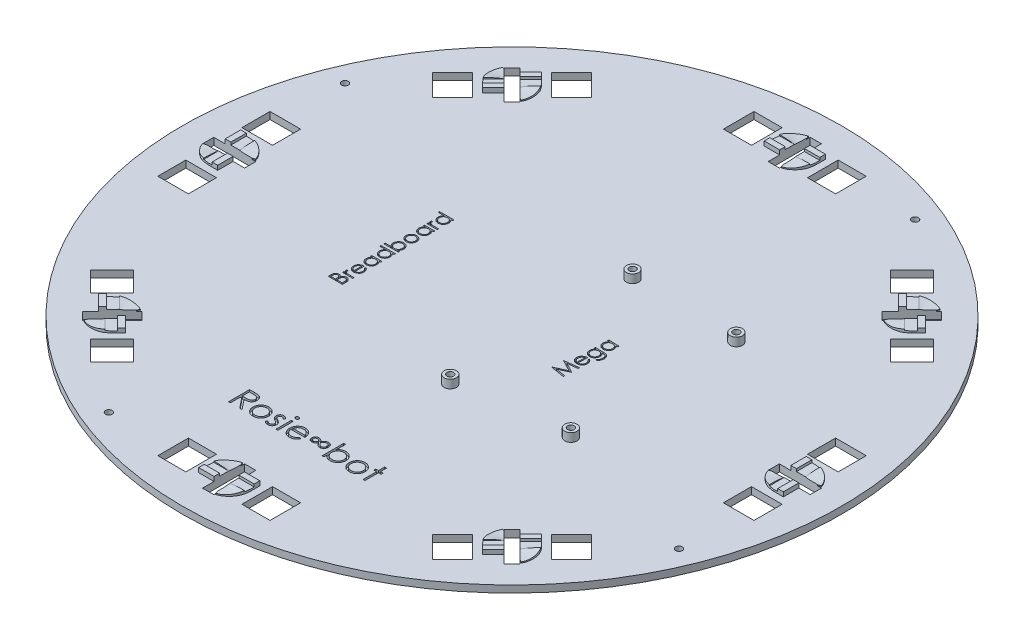
SolidWorks part; units mm, degrees
ref_plane "Front" through (0, 0, 0) normal (0, 0, 1) x (1, 0, 0)
ref_plane "Top" through (0, 0, 0) normal (0, 1, 0) x (1, 0, 0)
ref_plane "Right" through (0, 0, 0) normal (1, 0, 0) x (0, 0, -1)
sketch "Sketch1" plane through (0, 0, 0) normal (0, 1, 0) x (1, 0, 0)
  circle A0 centre (0, 0) radius 149.225
  dimension "D1" = 298.45
extrude "Boss-Extrude1" add sketch "Sketch1" along normal blind 3.175 contours A0
sketch "Sketch2" plane through (0, 3.175, 0) normal (0, 1, 0) x (1, 0, 0)
  line L1 (-2.54, -137.5833) -> (2.54, -137.5833)
  line L2 (-2.54, -137.5833) -> (-2.54, -118.5333)
  line L3 (-2.54, -118.5333) -> (2.54, -118.5333)
  line L4 (2.54, -137.5833) -> (2.54, -118.5333)
  circle A0 centre (0, 0) radius 149.225 construction
  point P4 (0, -118.5333)
  dimension "D1" = 5.08
  dimension "D2" = 19.05
  dimension "D3" = 137.5833
extrude "Cut-Extrude1" cut sketch "Sketch2" against normal up to next and the other way through all contours L1 L4 L3 L2
sketch "Sketch4" plane through (0, 3.175, 0) normal (0, 1, 0) x (1, 0, 0)
  line L0 (0, -128.0583) -> (-2.9434, -118.9995) construction
  line L1 (-2.9434, -118.9995) -> (0, -128.0583) construction
  line L2 (0, -128.0583) -> (-5.5987, -120.3525) construction
  line L3 (0, -128.0583) -> (-7.7059, -122.4597) construction
  line L4 (0, -128.0583) -> (-9.0588, -125.115) construction
  line L5 (0, -128.0583) -> (-9.525, -128.0583) construction
  line L9 (2.54, -118.5333) -> (-2.54, -118.5333) construction
  line L10 (2.54, -118.5333) -> (2.54, -137.5833) construction
  line L11 (-2.54, -118.5333) -> (-2.54, -137.5833) construction
  line L12 (2.54, -137.5833) -> (-2.54, -137.5833) construction
  circle A0 centre (0, -128.0583) radius 9.525 construction
  point P16 (0, -118.5333)
  point P19 (2.54, -128.0583)
  dimension "D1" = 18
  dimension "D2" = 18
  dimension "D3" = 18
  dimension "D4" = 18
  dimension "D5" = 18
ref_plane "Plane1" through (-37.6354, 0, 12.2285) normal (0.9511, 0, -0.309) x (-0.309, 0, -0.9511)
ref_plane "Plane2" through (-60.8954, 0, 44.2431) normal (0.809, 0, -0.5878) x (-0.5878, 0, -0.809)
ref_plane "Plane3" through (-60.8954, 0, 83.8153) normal (0.5878, 0, -0.809) x (-0.809, 0, -0.5878)
ref_plane "Plane4" through (-37.6354, 0, 115.8299) normal (0.309, 0, -0.9511) x (-0.9511, 0, -0.309)
ref_plane "Plane5" through (0, 0, 128.0583) normal (0, 0, -1) x (-1, 0, 0)
sketch "Sketch5" plane through (-37.6354, 0, 12.2285) normal (0.9511, 0, -0.309) x (-0.309, 0, -0.9511)
  line L0 (-111.947, 3.175) -> (-130.0646, 3.175) construction
  line L1 (-113.5711, 3.175) -> (-112.2657, 3.175)
  line L2 (-113.5711, 3.175) -> (-113.5711, 3.683)
  line L3 (-113.5711, 3.683) -> (-112.2657, 3.683)
  line L4 (-112.2657, 3.175) -> (-112.2657, 3.683)
  dimension "D2" = 0.508
sketch "Sketch6" plane through (-60.8954, 0, 44.2431) normal (0.809, 0, -0.5878) x (-0.5878, 0, -0.809)
  line L0 (-94.4025, 3.175) -> (-109.8143, 3.175) construction
  line L1 (-99.2801, 3.175) -> (-94.0764, 3.175)
  line L2 (-99.2801, 3.175) -> (-99.2801, 3.775)
  line L3 (-99.2801, 3.775) -> (-94.0764, 3.775)
  line L4 (-94.0764, 3.175) -> (-94.0764, 3.775)
  dimension "D2" = 0.6
sketch "Sketch7" plane through (-60.8954, 0, 83.8153) normal (0.5878, 0, -0.809) x (-0.809, 0, -0.5878)
  line L0 (-67.6172, 3.175) -> (-78.8146, 3.175) construction
  line L1 (-72.1312, 3.175) -> (-65.7458, 3.175)
  line L2 (-72.1312, 3.175) -> (-72.1312, 4.075)
  line L3 (-72.1312, 4.075) -> (-65.7458, 4.075)
  line L4 (-65.7458, 3.175) -> (-65.7458, 4.075)
  dimension "D2" = 0.9
sketch "Sketch10" plane through (-37.6354, 0, 115.8299) normal (0.309, 0, -0.9511) x (-0.9511, 0, -0.309)
  line L0 (-39.5722, 3.175) -> (-30.5134, 3.175) construction
  line L1 (-36.9015, 3.175) -> (-30.0472, 3.175)
  line L2 (-36.9015, 3.175) -> (-36.9015, 4.475)
  line L3 (-36.9015, 4.475) -> (-30.0472, 4.475)
  line L4 (-30.0472, 3.175) -> (-30.0472, 4.475)
  dimension "D3" = 1.3
sketch "Sketch11" plane through (0, 0, 128.0583) normal (0, 0, -1) x (-1, 0, 0)
  line L0 (0, 3.175) -> (9.525, 3.175) construction
  line L1 (2.54, 3.175) -> (9.525, 3.175)
  line L2 (2.54, 3.175) -> (2.54, 4.575)
  line L3 (2.54, 4.575) -> (9.525, 4.575)
  line L4 (9.525, 3.175) -> (9.525, 4.575)
  dimension "D3" = 1.4
loft "Loft1" add profiles "Sketch5", "Sketch6", "Sketch7", "Sketch10", "Sketch11" connector at (-2.54, 3.683, 120.241) connector at (-2.54, 3.775, 124.5623) connector at (-2.54, 4.075, 126.2129) connector at (-2.54, 4.475, 127.233) connector at (-2.54, 4.575, 128.0583)
sketch "Sketch13" plane through (-104.9799, 0, 128.0583) normal (0, 0, -1) x (-1, 0, 0)
  line L6 (-95.4549, 3.175) -> (-102.4399, 3.175)
  line L7 (-95.4549, 3.175) -> (-95.4549, 4.575)
  line L8 (-95.4549, 4.575) -> (-102.4399, 4.575)
  line L9 (-102.4399, 3.175) -> (-102.4399, 4.575)
extrude "Boss-Extrude4" add sketch "Sketch13" against normal blind 1.7907
sketch "Sketch25" plane through (0, 0, 129.849) normal (0, 0, 1) x (1, 0, 0)
  line L0 (-9.525, 4.575) -> (-2.54, 4.575) construction
  line L1 (-9.525, 3.175) -> (-2.54, 3.175)
  line L2 (-9.525, 3.175) -> (-9.525, 5.175)
  line L3 (-9.525, 5.175) -> (-2.54, 5.175)
  line L4 (-2.54, 3.175) -> (-2.54, 5.175)
  dimension "D1" = 0.6
extrude "Boss-Extrude5" add sketch "Sketch25" along normal blind 2.54
sketch "Sketch26" plane through (-2.54, 0, 0) normal (1, 0, 0) x (0, 0, -1)
  line L0 (-118.5333, 0) -> (-137.5833, 0) construction
  line L1 (-129.849, 5.175) -> (-125.749, 5.175)
  line L2 (-129.849, 5.175) -> (-129.849, 4)
  line L3 (-129.849, 4) -> (-125.749, 4)
  line L4 (-125.749, 5.175) -> (-125.749, 4)
  dimension "D1" = 4.1
  dimension "D2" = 4
extrude "Cut-Extrude8" cut sketch "Sketch26" against normal up to next
sketch "Sketch14" plane through (-2.54, 0, 0) normal (1, 0, 0) x (0, 0, -1)
  line L0 (-128.0583, 3.175) -> (-128.0583, 0) construction
  line L1 (-118.5333, 0) -> (-137.5833, 0) construction
ref_plane "Plane6" through (0, 0, 0) normal (1, 0, 0) x (0, 0, -1)
sketch "Sketch15" plane through (0, 0, 0) normal (1, 0, 0) x (0, 0, -1)
  line L0 (-128.0583, 0) -> (-128.0583, 3.175) construction
pattern_circular "CirPattern1" count 2 over 360 about axis through (0, 0, 128.0583) along (0, 1, 0) of "Loft1", "Boss-Extrude5", "Boss-Extrude4", "Cut-Extrude8" reverse direction yes
ref_axis "Axis1" through (0, 50, 0) along (0, -1, 0)
pattern_circular "CirPattern5" count 8 over 360 about axis through (0, 50, 0) along (0, -1, 0) of "CirPattern1", "Cut-Extrude1"
sketch "Sketch18" plane through (0, 3.175, 0) normal (0, 1, 0) x (1, 0, 0)
  line L0 (12.7, 40.64) -> (60.96, 40.64) construction
  line L1 (12.7, 40.64) -> (12.7, -40.64) construction
  line L2 (60.96, -34.29) -> (12.7, -34.29) construction
  line L3 (60.96, -34.29) -> (60.96, 40.64) construction
  line L4 (0, -149.225) -> (0, 149.225) construction
  line L5 (0, -1.7463) -> (0, 1.7463) construction
  line L6 (-149.225, 0) -> (149.225, 0) construction
  line L7 (12.7, 41.91) -> (12.7, 40.64) construction
  circle A0 centre (12.7, 41.91) radius 2.77
  circle A1 centre (12.7, -40.64) radius 2.77
  circle A2 centre (60.96, -34.29) radius 2.77
  circle A3 centre (60.96, 40.64) radius 2.77
  circle A4 centre (12.7, -40.64) radius 1.5
  circle A5 centre (12.7, 41.91) radius 1.5
  circle A6 centre (60.96, 40.64) radius 1.5
  circle A7 centre (60.96, -34.29) radius 1.5
  circle A8 centre (0, 0) radius 149.225 construction
  point P22 (12.7, 0)
  dimension "D7" = 12.7
  dimension "D5" = 3
  dimension "D6" = 1.27
  dimension "D1" = 82.55
  dimension "D2" = 74.93
  dimension "D3" = 48.26
  dimension "D4" = 1.27
sketch "Sketch19" plane through (0, 3.175, 0) normal (0, 1, 0) x (1, 0, 0)
  line L0 (-53.4609, -129.066) -> (0, 0) construction
  line L1 (0, -149.225) -> (0, 149.225) construction
  circle A1 centre (-53.4609, -129.066) radius 1.5
  dimension "D1" = 139.7
  dimension "D4" = 3
  dimension "D5" = 22.5
extrude "Cut-Extrude2" cut sketch "Sketch19" against normal through all
pattern_circular "CirPattern7" count 4 over 360 about axis through (0, 50, 0) along (0, -1, 0) of "Cut-Extrude2"
extrude "Boss-Extrude3" add sketch "Sketch18" along normal blind 3.81
sketch "Sketch23" plane through (0, 3.175, 0) normal (0, 1, 0) x (1, 0, 0)
  line L9 (-2.54, -132.389) -> (-2.54, -137.5833) construction
  line L10 (-25.4, -121.1305) -> (-12.7, -121.1305)
  line L11 (-25.4, -121.1305) -> (-25.4, -134.9862)
  line L16 (-25.4, -134.9862) -> (-12.7, -134.9862)
  line L17 (-12.7, -121.1305) -> (-12.7, -134.9862)
  line L19 (2.54, -118.5333) -> (2.54, -123.7276) construction
  line L20 (0, -50) -> (0, 50) construction
  line L21 (12.7, -121.1305) -> (12.7, -134.9862)
  line L22 (25.4, -134.9862) -> (12.7, -134.9862)
  line L23 (25.4, -121.1305) -> (25.4, -134.9862)
  line L24 (25.4, -121.1305) -> (12.7, -121.1305)
  point P8 (-2.54, -134.9862)
  point P9 (2.54, -121.1305)
  dimension "D1" = 12.7
  dimension "D2" = 10.16
extrude "Cut-Extrude6" cut sketch "Sketch23" against normal through all
sketch "Sketch17" plane through (0, 3.175, 0) normal (0, 1, 0) x (1, 0, 0)
  line L0 (-31.75, -97.8162) -> (31.75, -97.8162) construction
  point P3 (0, -97.8162)
  dimension "D2" = 97.8162
  dimension "D1" = 63.5
pattern_circular "CirPattern8" count 8 over 360 about axis through (0, 50, 0) along (0, -1, 0) of "Cut-Extrude6"
sketch "Sketch16" plane through (0, 3.175, 0) normal (0, 1, 0) x (1, 0, 0)
  line L0 (-31.75, -97.8162) -> (31.75, -97.8162) construction
  text T0 "Rosie∞bot\r\n" font "Century Gothic" height in points 36
extrude "Cut-Extrude4" cut sketch "Sketch16" against normal blind 1.27
sketch "Sketch22" plane through (0, 3.175, 0) normal (0, 1, 0) x (1, 0, 0)
  line L0 (-50.8, 25.1735) -> (-50.8, -31.2294) construction
  text T0 "Breadboard"
  dimension "D1" = 50.8
extrude "Cut-Extrude5" cut sketch "Sketch22" against normal blind 1.27
sketch "Sketch24" plane through (0, 3.175, 0) normal (0, 1, 0) x (1, 0, 0)
  line L0 (35.4114, -12.631) -> (36.0762, 12.631) construction
  circle A0 centre (12.7, 41.91) radius 1.5 construction
  circle A1 centre (60.96, 40.64) radius 1.5 construction
  text T0 "Mega"
  point P12 (35.7438, 0)
extrude "Cut-Extrude7" cut sketch "Sketch24" against normal blind 1.27
